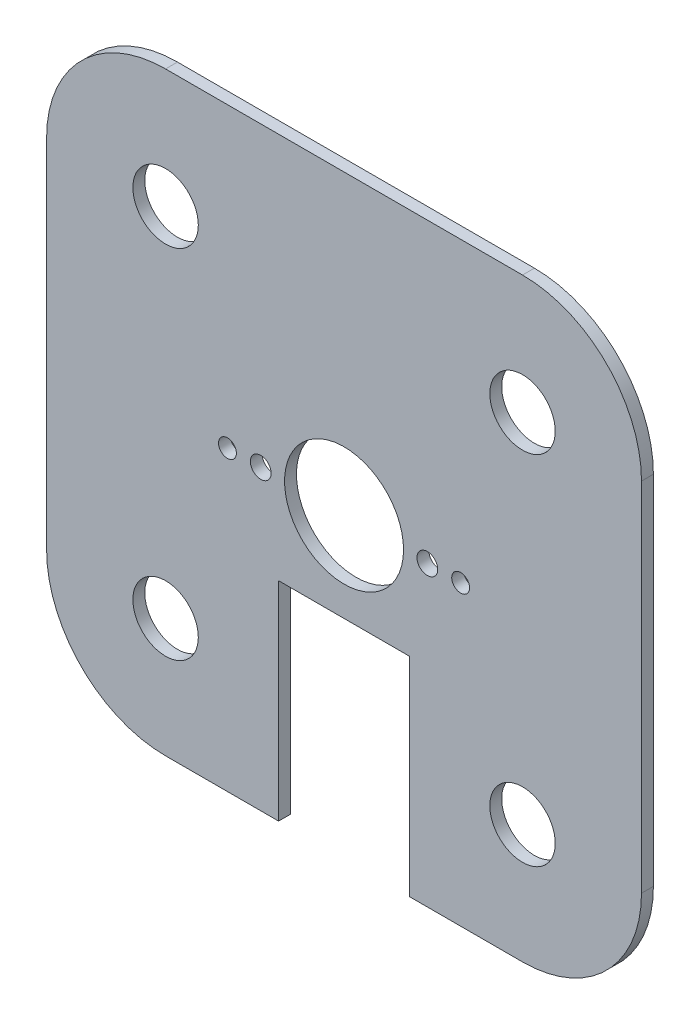
SolidWorks part; units mm, degrees
ref_plane "Front Plane" through (0, 0, 0) normal (0, 0, 1) x (1, 0, 0)
ref_plane "Top Plane" through (0, 0, 0) normal (0, 1, 0) x (1, 0, 0)
ref_plane "Right Plane" through (0, 0, 0) normal (1, 0, 0) x (0, 0, -1)
sketch "Sketch1" plane through (0, 0, 0) normal (0, 0, 1) x (1, 0, 0)
  line L0 (-9.8, 0) -> (9.8, 0) construction
  line L1 (-25, -25) -> (-5.5, -25)
  line L2 (-25, -25) -> (-25, 25)
  line L3 (-25, 25) -> (25, 25)
  line L4 (25, -25) -> (25, 25)
  line L5 (-25, -25) -> (25, 25) construction
  line L6 (-25, 25) -> (25, -25) construction
  line L7 (0, 0) -> (0, -7.5) construction
  line L8 (-5.5, -7.5) -> (5.5, -7.5)
  line L9 (5.5, -7.5) -> (5.5, -25)
  line L10 (-5.5, -7.5) -> (-5.5, -25)
  line L11 (0, -25) -> (25, -25)
  circle A0 centre (-15, 15) radius 2.75
  circle A1 centre (15, 15) radius 2.75
  circle A2 centre (15, -15) radius 2.75
  circle A3 centre (-15, -15) radius 2.75
  circle A4 centre (0, 0) radius 5
  circle A5 centre (7, 0) radius 0.875
  circle A6 centre (9.8, 0) radius 0.75
  circle A7 centre (-7, 0) radius 0.875
  circle A8 centre (-9.8, 0) radius 0.75
  point P0 (0, 0)
  point P31 (0, -5.8085)
  point P32 (0, -7.5)
  dimension "D6" = 5.5
  dimension "D7" = 10
  dimension "D8" = 1.75
  dimension "D9" = 1.5
  dimension "D2" = 15
  dimension "D3" = 15
  dimension "D4" = 15
  dimension "D5" = 15
  dimension "D10" = 7
  dimension "D11" = 9.8
  dimension "D12" = 19.6
  dimension "D13" = 14
  dimension "D14" = 11
  dimension "D15" = 7.5
  dimension "D16" = 10
extrude "Boss-Extrude1" add sketch "Sketch1" along normal blind 1 contours L9 L11 L4 L3 L2 L1 L10 L8 A8 A7 A6 A5 A4 A3 A2 A1 A0 region at (-24.2929, 0, 0)
fillet "Fillet1" radius 10 1 edges at (-25, -25, 0.5) type face fillet first side face at (-15.25, -25, 0.5) second side face at (-25, 0, 0.5)
fillet "Fillet2" radius 10 1 edges at (-25, 25, 0.5)
fillet "Fillet3" radius 10 1 edges at (25, -25, 0.5)
fillet "Fillet4" radius 10 1 edges at (25, 25, 0.5)
